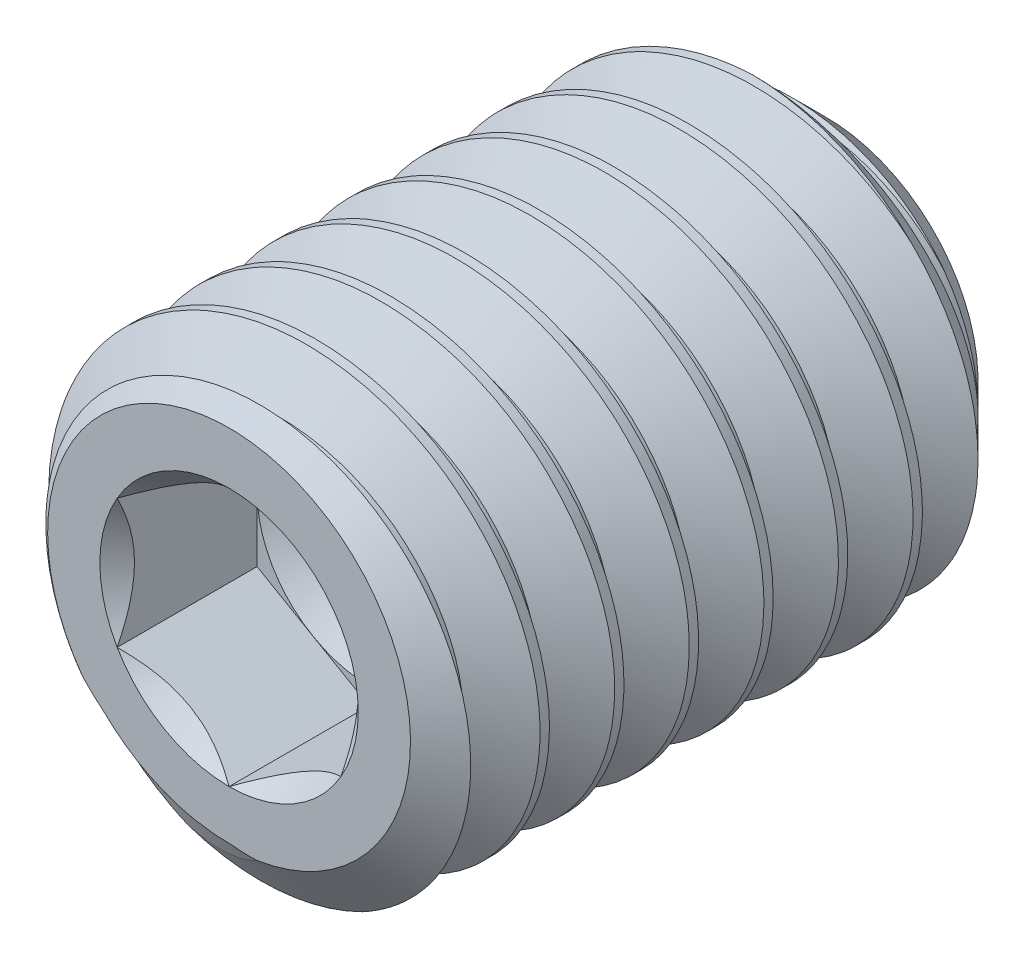
SolidWorks part; units mm, degrees
ref_plane "Front" through (0, 0, 0) normal (0, 0, 1) x (1, 0, 0)
ref_plane "Top" through (0, 0, 0) normal (0, 1, 0) x (1, 0, 0)
ref_plane "Right" through (0, 0, 0) normal (1, 0, 0) x (0, 0, -1)
sketch "Sketch22" plane through (0, 0, 0) normal (1, 0, 0) x (0, 0, -1)
  line L0 (-3.175, 0) -> (-3.175, 1.9304)
  line L1 (-3.175, 1.9304) -> (-2.8371, 2.413)
  line L2 (-2.8371, 2.413) -> (2.3813, 2.413)
  line L3 (2.3813, 2.413) -> (3.175, 1.6193)
  line L4 (-0.2279, 2.413) -> (-0.2279, -2.413) construction
  line L5 (3.175, 0) -> (-3.175, 0)
  line L7 (3.175, 0) -> (3.175, 1.6193)
  line L10 (-3.175, 1.9304) -> (-3.175, -1.9304) construction
  point P13 (-0.2279, 0)
  dimension "Length" = 6.35
  dimension "D3" = 35
  dimension "D1" = 3.8608
  dimension "Dia" = 4.826
  dimension "D2" = 0.7937
  dimension "D4" = 45
revolve "Revolve1" add sketch "Sketch22" angle 360 about L5
ref_plane "Plane1" through (0, 0, -3.175) normal (0, 0, 1) x (1, 0, 0)
sketch "Sketch27" plane through (0, 0, -3.175) normal (0, 0, 1) x (1, 0, 0)
  circle A0 centre (0, 0) radius 2.413 construction
  circle A1 centre (0, 0) radius 2.413
curve "Helix/Spiral1" pitch 0.7937 height 7.1437 radius 2.413 centre (0, 0, -3.175) axis (0, 0, 1) start towards (1, 0, 0)
sketch "Sketch28" plane through (0, 0, 0) normal (1, 0, 0) x (0, 0, -1)
  line L0 (3.175, 2.413) -> (3.8695, 2.413)
  line L1 (3.8695, 2.413) -> (3.5719, 1.8974)
  line L2 (3.5719, 1.8974) -> (3.4727, 1.8974)
  line L3 (3.4727, 1.8974) -> (3.175, 2.413)
  line L4 (3.3238, 2.1552) -> (3.7207, 2.1552) construction
  line L6 (-2.8371, 2.413) -> (2.3813, 2.413) construction
  line L7 (3.175, 2.6543) -> (3.175, -2.6543) construction
  dimension "D1" = 0.0992
  dimension "D3" = 60
  dimension "D2" = 0.3969
sweep "Cut-Sweep2" cut profiles "Sketch28" path "Helix/Spiral1" align with end faces yes
sketch "Sketch23" plane through (0, 0, 3.175) normal (0, 0, 1) x (1, 0, 0)
  line L1 (0, 1.3748) -> (-1.1906, 0.6874)
  line L2 (-1.1906, 0.6874) -> (-1.1906, -0.6874)
  line L3 (-1.1906, -0.6874) -> (0, -1.3748)
  line L4 (0, -1.3748) -> (1.1906, -0.6874)
  line L5 (1.1906, -0.6874) -> (1.1906, 0.6874)
  line L6 (1.1906, 0.6874) -> (0, 1.3748)
  circle A0 centre (0, 0) radius 1.1906 construction
  dimension "Hex" = 2.3813
extrude "Cut-Extrude10" cut sketch "Sketch23" against normal blind 1.4883
sketch "Sketch24" plane through (0, 0, 3.175) normal (0, 0, 1) x (1, 0, 0)
  circle A0 centre (0, 0) radius 1.3748
extrude "Cut-Extrude11" cut sketch "Sketch24" against normal through all draft 45
sketch "Sketch26" plane through (0, 0, 1.6867) normal (0, 0, 1) x (1, 0, 0)
  circle A0 centre (0, 0) radius 1.1906 construction
  circle A1 centre (0, 0) radius 1.1906
extrude "Cut-Extrude12" cut sketch "Sketch26" against normal through all draft 60
sketch "Sketch30" plane through (0, 0, 0) normal (1, 0, 0) x (0, 0, -1)
  line L0 (-2.8371, 2.413) -> (2.3813, 2.413) construction
  line L1 (-3.175, 0) -> (-3.175, 1.9304) construction
  line L2 (3.175, 0) -> (3.175, 1.6193) construction
  point P0 (-3.175, 2.413)
  point P1 (3.175, 2.413)
  point P2 (3.175, -2.413)
  point P11 (1.1906, -2.413)
  dimension "D1" = 1.9844
equation "\"D1@Sketch28\" = \"D4@Helix/Spiral1\" * .125"
equation "\"D3@Helix/Spiral1\" = \"Length@Sketch22\" + \"D4@Helix/Spiral1\""
equation "\"D1@Sketch30\" = \"D4@Helix/Spiral1\" * 2.5"
equation "\"hex Depth@Cut-Extrude10\" = \"Hex@Sketch23\" * .625"
equation "\"D2@Sketch28\" = \"D4@Helix/Spiral1\" * .5"
equation "\"D1@Sketch22\" = \"Dia@Sketch22\" * .8"
equation "\"D2@Sketch22\" = \"D4@Helix/Spiral1\""
